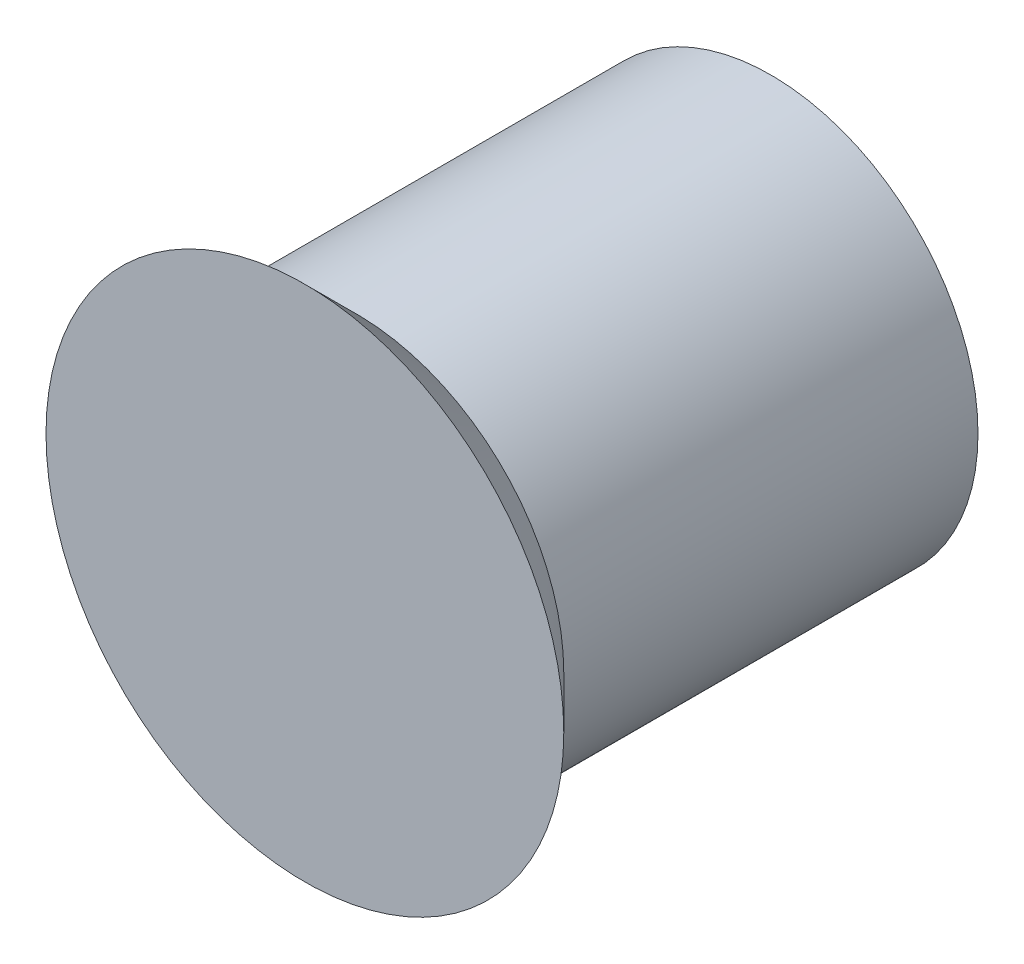
SolidWorks part; units mm, degrees
ref_plane "Ön Düzlem" through (0, 0, 0) normal (0, 0, 1) x (1, 0, 0)
ref_plane "Üst Düzlem" through (0, 0, 0) normal (0, 1, 0) x (1, 0, 0)
ref_plane "Sağ Düzlem" through (0, 0, 0) normal (1, 0, 0) x (0, 0, -1)
sketch "Çizim1" plane through (0, 0, 0) normal (0, 0, 1) x (1, 0, 0)
  circle A0 centre (0, 0) radius 4
  dimension "D1" = 8
extrude "Yükseklik-Ekstrüzyon1" add sketch "Çizim1" along normal blind 8
sketch "Çizim2" plane through (0, 0, 8) normal (0, 0, 1) x (1, 0, 0)
  circle A0 centre (0, 0) radius 4
extrude "Yükseklik-Ekstrüzyon2" add sketch "Çizim2" along normal blind 1 draft 45 draft outward yes
